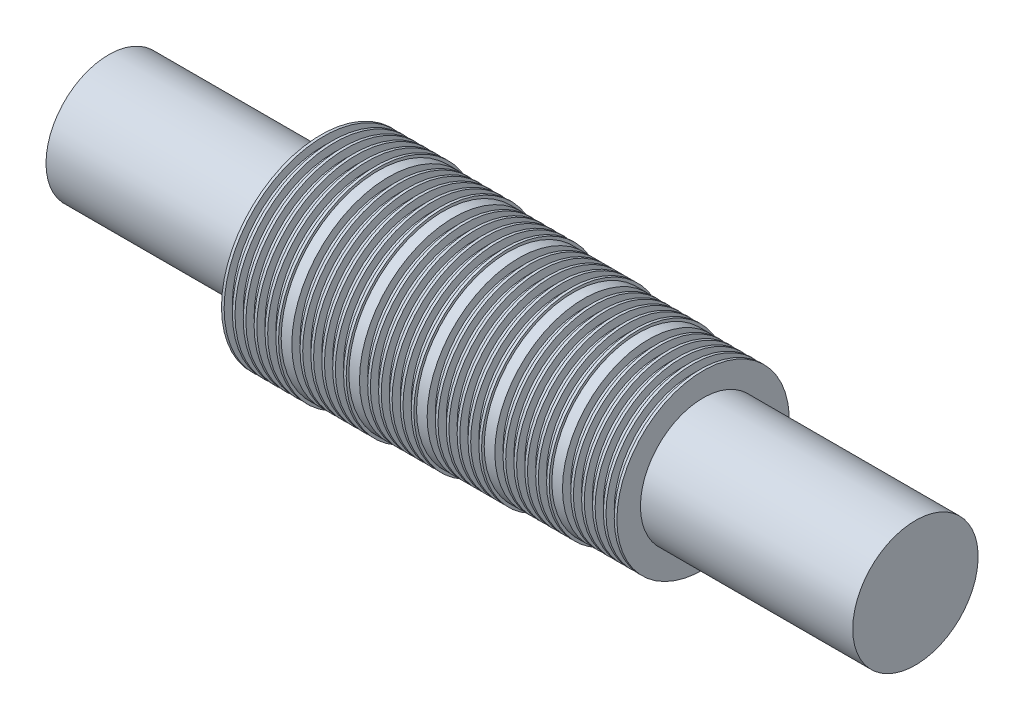
SolidWorks part; units mm, degrees
ref_plane "Front Plane" through (0, 0, 0) normal (0, 0, 1) x (1, 0, 0)
ref_plane "Top Plane" through (0, 0, 0) normal (0, 1, 0) x (1, 0, 0)
ref_plane "Right Plane" through (0, 0, 0) normal (1, 0, 0) x (0, 0, -1)
sketch "Sketch1" plane through (0, 0, 0) normal (0, 0, 1) x (1, 0, 0)
  line L24 (20.574, 9.525) -> (20.574, 8.7376)
  line L25 (20.574, 8.7376) -> (21.3614, 8.7376)
  line L26 (21.3614, 8.7376) -> (21.3614, 9.525)
  line L27 (21.3614, 9.525) -> (21.6154, 9.525)
  line L28 (21.6154, 9.525) -> (21.6154, 8.7376)
  line L29 (21.6154, 8.7376) -> (22.4028, 8.7376)
  line L30 (22.4028, 8.7376) -> (22.4028, 9.525)
  line L31 (22.4028, 9.525) -> (22.6568, 9.525)
  line L32 (22.6568, 9.525) -> (22.6568, 8.7376)
  line L33 (22.6568, 8.7376) -> (23.4442, 8.7376)
  line L34 (23.4442, 8.7376) -> (23.4442, 9.525)
  line L35 (23.4442, 9.525) -> (23.6982, 9.525)
  line L36 (23.6982, 9.525) -> (23.6982, 8.7376)
  line L37 (23.6982, 8.7376) -> (24.4856, 8.7376)
  line L38 (24.4856, 8.7376) -> (24.4856, 9.525)
  line L39 (24.4856, 9.525) -> (24.7396, 9.525)
  line L40 (24.7396, 9.525) -> (24.7396, 8.7376)
  line L41 (24.7396, 8.7376) -> (25.527, 8.7376)
  line L42 (25.527, 8.7376) -> (25.527, 9.525)
  line L43 (25.527, 9.525) -> (25.781, 9.525)
  line L44 (25.781, 9.525) -> (25.781, 9.271)
  line L45 (25.781, 9.271) -> (26.797, 9.271)
  line L46 (26.797, 9.271) -> (26.797, 8.4836)
  line L47 (26.797, 8.4836) -> (27.5844, 8.4836)
  line L48 (27.5844, 8.4836) -> (27.5844, 9.271)
  line L49 (27.5844, 9.271) -> (27.8384, 9.271)
  line L50 (27.8384, 9.271) -> (27.8384, 8.4836)
  line L51 (27.8384, 8.4836) -> (28.6258, 8.4836)
  line L52 (28.6258, 8.4836) -> (28.6258, 9.271)
  line L53 (28.6258, 9.271) -> (28.8798, 9.271)
  line L54 (28.8798, 9.271) -> (28.8798, 8.4836)
  line L55 (28.8798, 8.4836) -> (29.6672, 8.4836)
  line L56 (29.6672, 8.4836) -> (29.6672, 9.271)
  line L57 (29.6672, 9.271) -> (29.9212, 9.271)
  line L58 (29.9212, 9.271) -> (29.9212, 8.4836)
  line L59 (29.9212, 8.4836) -> (30.7086, 8.4836)
  line L60 (30.7086, 8.4836) -> (30.7086, 9.271)
  line L61 (30.7086, 9.271) -> (30.9626, 9.271)
  line L62 (30.9626, 9.271) -> (30.9626, 8.4836)
  line L63 (30.9626, 8.4836) -> (31.75, 8.4836)
  line L64 (31.75, 8.4836) -> (31.75, 9.271)
  line L65 (31.75, 9.271) -> (32.004, 9.271)
  line L66 (32.004, 9.271) -> (32.004, 9.017)
  line L67 (32.004, 9.017) -> (33.02, 9.017)
  line L68 (33.02, 9.017) -> (33.02, 8.2296)
  line L69 (33.02, 8.2296) -> (33.8074, 8.2296)
  line L70 (33.8074, 8.2296) -> (33.8074, 9.017)
  line L71 (33.8074, 9.017) -> (34.0614, 9.017)
  line L72 (34.0614, 9.017) -> (34.0614, 8.2296)
  line L73 (34.0614, 8.2296) -> (34.8488, 8.2296)
  line L74 (34.8488, 8.2296) -> (34.8488, 9.017)
  line L75 (34.8488, 9.017) -> (35.1028, 9.017)
  line L76 (35.1028, 9.017) -> (35.1028, 8.2296)
  line L77 (35.1028, 8.2296) -> (35.8902, 8.2296)
  line L78 (35.8902, 8.2296) -> (35.8902, 9.017)
  line L79 (35.8902, 9.017) -> (36.1442, 9.017)
  line L80 (36.1442, 9.017) -> (36.1442, 8.2296)
  line L81 (36.1442, 8.2296) -> (36.9316, 8.2296)
  line L82 (36.9316, 8.2296) -> (36.9316, 9.017)
  line L83 (36.9316, 9.017) -> (37.1856, 9.017)
  line L84 (37.1856, 9.017) -> (37.1856, 8.2296)
  line L85 (37.1856, 8.2296) -> (37.973, 8.2296)
  line L86 (37.973, 8.2296) -> (37.973, 9.017)
  line L87 (37.973, 9.017) -> (38.227, 9.017)
  line L88 (38.227, 9.017) -> (38.227, 8.763)
  line L89 (38.227, 8.763) -> (39.243, 8.763)
  line L90 (39.243, 8.763) -> (39.243, 7.9756)
  line L91 (39.243, 7.9756) -> (40.0304, 7.9756)
  line L92 (40.0304, 7.9756) -> (40.0304, 8.763)
  line L93 (40.0304, 8.763) -> (40.2844, 8.763)
  line L94 (40.2844, 8.763) -> (40.2844, 7.9756)
  line L95 (40.2844, 7.9756) -> (41.0718, 7.9756)
  line L96 (41.0718, 7.9756) -> (41.0718, 8.763)
  line L97 (41.0718, 8.763) -> (41.3258, 8.763)
  line L98 (41.3258, 8.763) -> (41.3258, 7.9756)
  line L99 (41.3258, 7.9756) -> (42.1132, 7.9756)
  line L100 (42.1132, 7.9756) -> (42.1132, 8.763)
  line L101 (42.1132, 8.763) -> (42.3672, 8.763)
  line L102 (42.3672, 8.763) -> (42.3672, 7.9756)
  line L103 (42.3672, 7.9756) -> (43.1546, 7.9756)
  line L104 (43.1546, 7.9756) -> (43.1546, 8.763)
  line L105 (43.1546, 8.763) -> (43.4086, 8.763)
  line L106 (43.4086, 8.763) -> (43.4086, 7.9756)
  line L107 (43.4086, 7.9756) -> (44.196, 7.9756)
  line L108 (44.196, 7.9756) -> (44.196, 8.763)
  line L109 (44.196, 8.763) -> (44.45, 8.763)
  line L110 (44.45, 8.763) -> (44.45, 8.509)
  line L111 (44.45, 8.509) -> (45.466, 8.509)
  line L112 (45.466, 8.509) -> (45.466, 7.7216)
  line L113 (45.466, 7.7216) -> (46.2534, 7.7216)
  line L114 (46.2534, 7.7216) -> (46.2534, 8.509)
  line L115 (46.2534, 8.509) -> (46.5074, 8.509)
  line L116 (46.5074, 8.509) -> (46.5074, 7.7216)
  line L117 (46.5074, 7.7216) -> (47.2948, 7.7216)
  line L118 (47.2948, 7.7216) -> (47.2948, 8.509)
  line L119 (47.2948, 8.509) -> (47.5488, 8.509)
  line L120 (47.5488, 8.509) -> (47.5488, 7.7216)
  line L121 (47.5488, 7.7216) -> (48.3362, 7.7216)
  line L122 (48.3362, 7.7216) -> (48.3362, 8.509)
  line L123 (48.3362, 8.509) -> (48.5902, 8.509)
  line L124 (48.5902, 8.509) -> (48.5902, 7.7216)
  line L125 (48.5902, 7.7216) -> (49.3776, 7.7216)
  line L126 (49.3776, 7.7216) -> (49.3776, 8.509)
  line L127 (49.3776, 8.509) -> (49.6316, 8.509)
  line L128 (49.6316, 8.509) -> (49.6316, 7.7216)
  line L129 (49.6316, 7.7216) -> (50.419, 7.7216)
  line L130 (50.419, 7.7216) -> (50.419, 8.509)
  line L131 (50.419, 8.509) -> (50.673, 8.509)
  line L132 (50.673, 8.509) -> (50.673, 8.255)
  line L133 (50.673, 8.255) -> (51.689, 8.255)
  line L134 (51.689, 8.255) -> (51.689, 7.4676)
  line L135 (51.689, 7.4676) -> (52.4764, 7.4676)
  line L136 (52.4764, 7.4676) -> (52.4764, 8.255)
  line L137 (52.4764, 8.255) -> (52.7304, 8.255)
  line L138 (52.7304, 8.255) -> (52.7304, 7.4676)
  line L139 (52.7304, 7.4676) -> (53.5178, 7.4676)
  line L140 (53.5178, 7.4676) -> (53.5178, 8.255)
  line L141 (53.5178, 8.255) -> (53.7718, 8.255)
  line L142 (53.7718, 8.255) -> (53.7718, 7.4676)
  line L143 (53.7718, 7.4676) -> (54.5592, 7.4676)
  line L144 (54.5592, 7.4676) -> (54.5592, 8.255)
  line L145 (54.5592, 8.255) -> (54.8132, 8.255)
  line L146 (54.8132, 8.255) -> (54.8132, 7.4676)
  line L147 (54.8132, 7.4676) -> (55.6006, 7.4676)
  line L148 (55.6006, 7.4676) -> (55.6006, 8.255)
  line L149 (55.6006, 8.255) -> (55.8546, 8.255)
  line L150 (55.8546, 8.255) -> (55.8546, 7.4676)
  line L151 (55.8546, 7.4676) -> (56.642, 7.4676)
  line L152 (56.642, 7.4676) -> (56.642, 8.255)
  line L153 (56.642, 8.255) -> (56.896, 8.255)
  line L156 (20.32, 6) -> (0, 6)
  line L157 (0, 6) -> (0, 0)
  line L158 (0, 0) -> (61.976, 0)
  line L160 (20.574, 9.525) -> (20.32, 9.525)
  line L161 (20.32, 9.525) -> (20.32, 6)
  line L162 (56.896, 6) -> (77.216, 6)
  line L163 (77.216, 6) -> (77.216, 0)
  line L164 (77.216, 0) -> (61.976, 0)
  line L165 (56.896, 8.255) -> (56.896, 6)
  point P5 (20.447, 9.525)
  point P6 (67.056, 6)
  dimension "D1" = 6
  dimension "D9" = 20.32
  dimension "D3" = 0.254
  dimension "D4" = 0.7874
  dimension "D5" = 0.7874
  dimension "D7" = 1.016
  dimension "D10" = 6
  dimension "D11" = 20.32
  dimension "D2" = 9.525
revolve "Revolve1" add sketch "Sketch1" angle 360 about L158
equation "\"kero_radius\"=0.23622in"
equation "\"D1@Sketch1\"=\"kero_radius\""
equation "\"lox_radius\"=0.23622in"
equation "\"Cavity_width\"=0.031in"
equation "\"tooth_width\"=0.01in"
equation "\"cavity_depth\"=0.031in"
equation "\"seal_step\"=0.01in"
equation "\"purge_length\"=0.04in"
equation "\"D3@Sketch1\"=\"tooth_width\""
equation "\"D4@Sketch1\"=\"Cavity_width\""
equation "\"D5@Sketch1\"=\"cavity_depth\""
equation "\"D7@Sketch1\"=\"purge_length\""
equation "\"D10@Sketch1\"=\"lox_radius\""
equation "\"lox_in_radius\"=.375in"
equation "\"bearing_radius\"= 0.629921"
equation "\"bearing_width\"=0.393701"
equation "\"insert_radius\" = 0.7in"
equation "\"recycle_groove width\" = 0.06in"
equation "\"recycle_groove_depth\" = 0.06in"
equation "\"N2_purge_width\"= .06in"
equation "\"N2_purge_depth\"= .06in"
equation "\"drain_width\"= .06in"
equation "\"drain_depth\"= .06in"
equation "\"radial_clearance\"= .002in"
equation "\"IPS_flange_width\"= .2in"
equation "\"IPS_flange_radius\" = 2.2in"
equation "\"IPS_LOX_male_radius\"= .9in"
equation "\"IPS_Kero_male_radius\" = .9in"
equation "\"IPS_radius\"= 1.5in"
equation "\"InsertLength\"= 1.47in"
equation "\"D2@Sketch1\"=\"lox_in_radius\""
